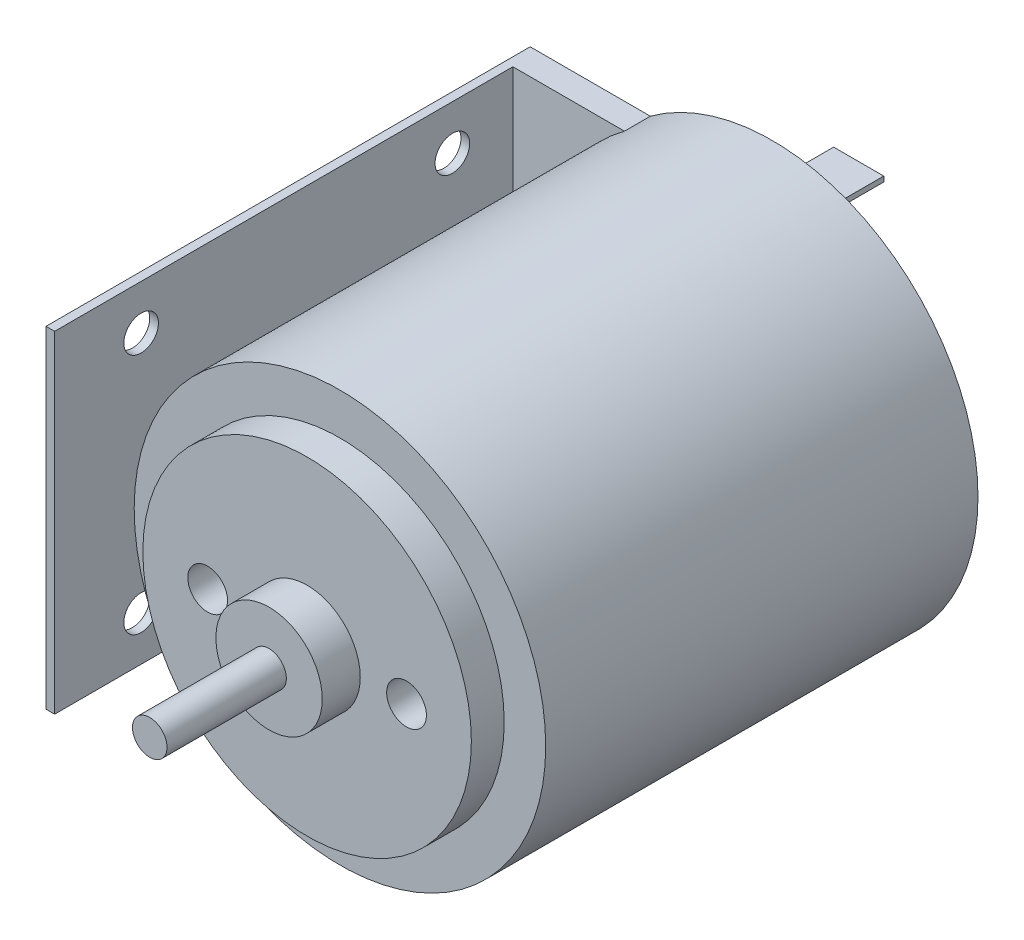
SolidWorks part; units mm, degrees
ref_plane "正面" through (0, 0, 0) normal (0, 0, 1) x (1, 0, 0)
ref_plane "平面" through (0, 0, 0) normal (0, 1, 0) x (1, 0, 0)
ref_plane "右側面" through (0, 0, 0) normal (1, 0, 0) x (0, 0, -1)
sketch "ｽｹｯﾁ2" plane through (0, 0, 0) normal (0, 0, 1) x (1, 0, 0)
  circle A0 centre (0, 0) radius 9.5
  circle A1 centre (0, 0) radius 11.9
  circle A2 centre (0, 0) radius 3.075
  circle A3 centre (0, 0) radius 1
  circle A4 centre (0, 0) radius 4.25
  dimension "D1" = 23.8
  dimension "D2" = 19
  dimension "D3" = 6.15
  dimension "D4" = 2
  dimension "D5" = 8.5
extrude "ﾎﾞｽ - 押し出し1" add sketch "ｽｹｯﾁ2" along normal blind 36 contours A3 region at (0, 0, 0)
extrude "ﾎﾞｽ - 押し出し2" add sketch "ｽｹｯﾁ2<4>" along normal blind 29.1 contours A2 A3 region at (-2.988, 0, 0)
sketch "ｽｹｯﾁ2<4>" plane through (0, 0, 0) normal (0, 0, 1) x (1, 0, 0) same geometry as "ｽｹｯﾁ2"
extrude "ﾎﾞｽ - 押し出し3" add sketch "ｽｹｯﾁ2<5>" along normal blind 26.9 and the other way blind 2 contours A4 A2 region at (-4.1298, 0, 0)
sketch "ｽｹｯﾁ2<5>" plane through (0, 0, 0) normal (0, 0, 1) x (1, 0, 0) same geometry as "ｽｹｯﾁ2"
extrude "ﾎﾞｽ - 押し出し4" add sketch "ｽｹｯﾁ2<6>" along normal blind 26.9 contours A0 A4 region at (-9.2313, 0, 0)
sketch "ｽｹｯﾁ2<6>" plane through (0, 0, 0) normal (0, 0, 1) x (1, 0, 0) same geometry as "ｽｹｯﾁ2"
extrude "ﾎﾞｽ - 押し出し5" add sketch "ｽｹｯﾁ2<7>" along normal blind 25 contours A1 A0 region at (-11.5634, 0, 0)
sketch "ｽｹｯﾁ2<7>" plane through (0, 0, 0) normal (0, 0, 1) x (1, 0, 0) same geometry as "ｽｹｯﾁ2"
ref_plane "平面1" through (0, 0, 26.9) normal (0, 0, 1) x (1, 0, 0)
ref_plane "平面2" through (0, 0, -10) normal (0, 0, -1) x (-1, 0, 0)
ref_plane "平面3" through (0, 0, 0) normal (0, 0, -1) x (-1, 0, 0)
sketch "ｽｹｯﾁ5" plane through (0, 0, 0) normal (0, 0, -1) x (-1, 0, 0)
  line L5 (1.45, -7.8068) -> (-1.45, -7.8068)
  line L6 (1.45, -7.8068) -> (1.45, -7.5068)
  line L11 (1.45, -7.5068) -> (-1.45, -7.5068)
  line L12 (-1.45, -7.8068) -> (-1.45, -7.5068)
  line L13 (1.45, -7.8068) -> (-1.45, -7.5068) construction
  line L14 (1.45, -7.5068) -> (-1.45, -7.8068) construction
  line L15 (-1.45, 8.3397) -> (1.45, 8.3397)
  line L16 (-1.45, 8.3397) -> (-1.45, 8.0397)
  line L17 (-1.45, 8.0397) -> (1.45, 8.0397)
  line L18 (1.45, 8.3397) -> (1.45, 8.0397)
  line L19 (-1.45, 8.3397) -> (1.45, 8.0397) construction
  line L20 (-1.45, 8.0397) -> (1.45, 8.3397) construction
  circle A0 centre (6.45, 0) radius 1
  circle A1 centre (-6.45, 0) radius 1
  point P4 (-0.6526, 8.1897)
  point P5 (0, 8.1897)
  point P6 (0, -7.6568)
  point P9 (1.8202, -7.6568)
  dimension "D3" = 2
  dimension "D4" = 2
  dimension "D1" = 6.45
  dimension "D2" = 6.45
  dimension "D5" = 2.9
  dimension "D6" = 0.3
  dimension "D7" = 2.9
  dimension "D8" = 0.3
extrude "ﾎﾞｽ - 押し出し6" add sketch "ｽｹｯﾁ5" along normal blind 5 contours L16 L15 L18 L17 | L6 L5 L12 L11
sketch "ｽｹｯﾁ6" plane through (0, 0, 0) normal (0, 0, -1) x (-1, 0, 0)
  circle A0 centre (6.45, 0) radius 1
  circle A1 centre (-6.45, 0) radius 1
  dimension "D1" = 6.45
  dimension "D2" = 6.45
hole_wizard "M2 ねじ穴2" positions "ｽｹｯﾁ9" profile "ｽｹｯﾁ10" tap size "M2" standard "IS"
sketch "ｽｹｯﾁ9" plane through (0, 0, 0) normal (0, 0, -1) x (-1, 0, 0)
  point P0 (-6.45, 0)
  point P3 (6.45, 0)
sketch "ｽｹｯﾁ10" plane through (6.45, 0, 0) normal (1, 0, 0) x (0, 1, 0)
  line L0 (0, 0) -> (0, 6.4807)
  line L1 (0, 6.4807) -> (0.8, 6)
  line L2 (0.8, 6) -> (0.8, 0)
  line L5 (0.8, 0) -> (0, 0)
  line L10 (0, 6.4807) -> (-0.8, 6) construction
  line L11 (0, -6.35) -> (0, 107.95) construction
  dimension "ねじ下穴ﾄﾞﾘﾙ直径" = 1.6
  dimension "ねじ下穴ﾄﾞﾘﾙの深さ" = 6
  dimension "ﾄﾞﾘﾙ角度" = 118
cosmetic thread "穴のねじ山2" parameters "D1"=4, "D2"=2
cosmetic thread "穴のねじ山3" parameters "D1"=4, "D2"=2
ref_plane "平面4" through (0, 0, 36.9) normal (0, 0, 1) x (1, 0, 0)
sketch "ｽｹｯﾁ14" plane through (0, 0, 26.9) normal (0, 0, 1) x (1, 0, 0)
  circle A0 centre (5.75, 0) radius 1.15
  circle A1 centre (-5.75, 0) radius 1.15
  dimension "D3" = 2.3
  dimension "D4" = 2.3
  dimension "D1" = 5.75
  dimension "D2" = 5.75
extrude "ｶｯﾄ - 押し出し1" cut sketch "ｽｹｯﾁ14" against normal blind 3
sketch "ｽｹｯﾁ15" plane through (0, 0, 0) normal (0, 0, -1) x (-1, 0, 0)
  line L1 (13.5, -9.589) -> (14, -9.589)
  line L2 (13.5, -9.589) -> (13.5, 9.589)
  line L3 (13.5, 9.589) -> (14, 9.589)
  line L4 (14, -9.589) -> (14, 9.589)
  line L5 (13.5, -9.589) -> (14, 9.589) construction
  line L6 (13.5, 9.589) -> (14, -9.589) construction
  point P0 (13.75, 0)
  dimension "D1" = 13.5
  dimension "D2" = 0.5
extrude "ﾎﾞｽ - 押し出し7" add sketch "ｽｹｯﾁ15" against normal blind 28 separate body
ref_plane "平面5" through (-24, 0, 0) normal (-1, 0, 0) x (0, 0, 1)
sketch "ｽｹｯﾁ16" plane through (-24, 0, 0) normal (-1, 0, 0) x (0, 0, 1)
  line L0 (0, 9.589) -> (0, -9.4889)
  line L1 (0, 13.09) -> (0, -13.09) construction
  line L2 (28, 9.589) -> (0, 9.589) construction
  line L3 (0, -9.4889) -> (1.5, -9.589)
  line L4 (28, -9.589) -> (0, -9.589) construction
  line L5 (1.5, -9.589) -> (1.5, 9.589)
  line L6 (1.5, 9.589) -> (0, 9.589)
  dimension "D1" = 1.5
ref_plane "平面6" through (-14, 0, 0) normal (-1, 0, 0) x (0, 0, 1)
sketch "ｽｹｯﾁ17" plane through (-14, 0, 0) normal (-1, 0, 0) x (0, 0, 1)
  line L0 (0, 9.589) -> (0, -9.589)
  line L1 (0, -9.589) -> (1.5, -9.589)
  line L2 (28, -9.589) -> (0, -9.589) construction
  line L3 (1.5, -9.589) -> (1.5, 9.589)
  line L4 (28, 9.589) -> (0, 9.589) construction
  line L5 (1.5, 9.589) -> (0, 9.589)
  dimension "D1" = 1.5
extrude "ﾎﾞｽ - 押し出し9" add sketch "ｽｹｯﾁ17" against normal blind 10
sketch "ｽｹｯﾁ18" plane through (-14, 0, 0) normal (-1, 0, 0) x (0, 0, 1)
  line L0 (0, 9.589) -> (0, -9.4889) construction
  line L1 (28, -9.589) -> (28, 9.589) construction
  circle A0 centre (5, 7) radius 1
  circle A1 centre (5, -7) radius 1
  circle A2 centre (23, 7) radius 1
  circle A3 centre (23, -7) radius 1
  point P8 (0, 0)
  dimension "D2" = 2
  dimension "D6" = 2
  dimension "D7" = 2
  dimension "D8" = 2
  dimension "D1" = 7
  dimension "D3" = 7
  dimension "D4" = 5
  dimension "D5" = 5
  dimension "D9" = 5
  dimension "D10" = 5
  dimension "D11" = 7
  dimension "D12" = 7
extrude "ｶｯﾄ - 押し出し2" cut sketch "ｽｹｯﾁ18" against normal blind 1
equation "\"D3@ｽｹｯﾁ18\"=\"D1@ｽｹｯﾁ18\""
equation "\"D5@ｽｹｯﾁ18\"=\"D4@ｽｹｯﾁ18\""
equation "\"D7@ｽｹｯﾁ18\"=\"D2@ｽｹｯﾁ18\""
equation "\"D11@ｽｹｯﾁ18\"=\"D1@ｽｹｯﾁ18\""
